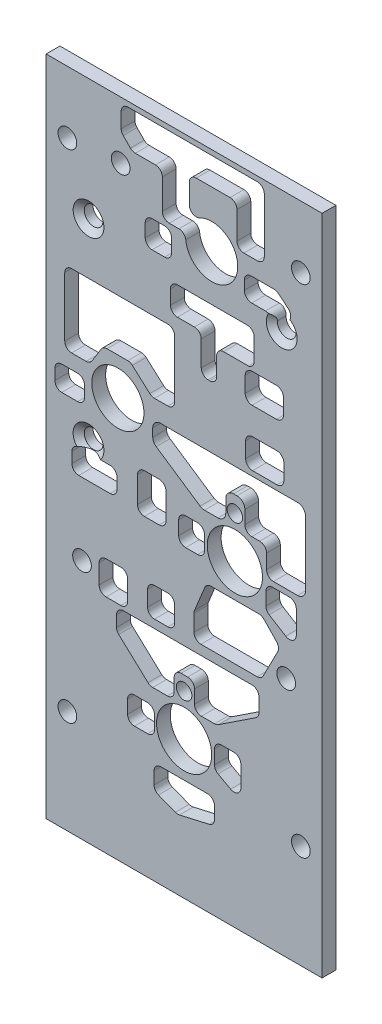
SolidWorks part; units mm, degrees
material "Acrylic (Medium-high impact)"
ref_plane "Front Plane" through (0, 0, 0) normal (0, 0, 1) x (1, 0, 0)
ref_plane "Top Plane" through (0, 0, 0) normal (0, 1, 0) x (1, 0, 0)
ref_plane "Right Plane" through (0, 0, 0) normal (1, 0, 0) x (0, 0, -1)
sketch "Sketch1" plane through (0, 0, 0) normal (0, 0, 1) x (1, 0, 0)
  line L8 (31.75, -152.4) -> (31.75, 0)
  line L9 (31.75, 0) -> (-31.75, 0)
  line L10 (-31.75, 0) -> (-31.75, -152.4)
  line L11 (-31.75, -152.4) -> (31.75, -152.4)
extrude "Boss-Extrude1" add sketch "Sketch1" against normal blind 3.175
hole_wizard "#6 Clearance Hole1" positions "Sketch3" profile "Sketch2" hole size "#6" standard "ANSI Inch" end condition up to next
sketch "Sketch3" plane through (0, 0, 0) normal (0, 0, 1) x (1, 0, 0)
  point P0 (-26.8605, -14.2875)
  point P2 (26.8605, -14.2875)
  point P4 (26.8605, -128.5875)
  point P6 (-26.8605, -128.5875)
sketch "Sketch2" plane through (-26.8605, -14.2875, 0) normal (1, 0, 0) x (0, -1, 0)
  line L0 (0, 0) -> (0, 3.175)
  line L1 (0, 3.175) -> (2.1526, 3.175)
  line L2 (2.1526, 3.175) -> (2.1526, 0)
  line L5 (2.1526, 0) -> (0, 0)
  line L11 (0, -6.35) -> (0, 107.95) construction
  dimension "Thru Hole Dia." = 4.3053
  dimension "Thru Hole Depth" = 3.175
hole_wizard "#6 Clearance Hole2" positions "Sketch5" profile "Sketch4" hole size "#6" standard "ANSI Inch" end condition up to next
sketch "Sketch5" plane through (0, 0, 0) normal (0, 0, 1) x (1, 0, 0)
  point P0 (-23.495, -96.8375)
  point P2 (23.495, -96.8375)
  point P4 (-14.605, -13.208)
sketch "Sketch4" plane through (-23.495, -96.8375, 0) normal (1, 0, 0) x (0, -1, 0)
  line L0 (0, 0) -> (0, 3.175)
  line L1 (0, 3.175) -> (2.1526, 3.175)
  line L2 (2.1526, 3.175) -> (2.1526, 0)
  line L5 (2.1526, 0) -> (0, 0)
  line L11 (0, -6.35) -> (0, 107.95) construction
  dimension "Thru Hole Dia." = 4.3053
  dimension "Thru Hole Depth" = 3.175
hole_wizard "1/2 (0.5) Diameter Hole1" positions "Sketch7" profile "Sketch6" hole size "1/2" standard "ANSI Inch" end condition up to next
sketch "Sketch7" plane through (0, 0, 0) normal (0, 0, 1) x (1, 0, 0)
  point P4 (11.684, -79.375)
  point P6 (0, -120.65)
sketch "Sketch6" plane through (11.684, -79.375, 0) normal (1, 0, 0) x (0, -1, 0)
  line L0 (0, 0) -> (0, 3.175)
  line L1 (0, 3.175) -> (6.35, 3.175)
  line L2 (6.35, 3.175) -> (6.35, 0)
  line L5 (6.35, 0) -> (0, 0)
  line L11 (0, -6.35) -> (0, 107.95) construction
  dimension "Thru Hole Dia." = 12.7
  dimension "Thru Hole Depth" = 3.175
hole_wizard "9/64 (0.14063) Diameter Hole1" positions "Sketch9" profile "Sketch8" hole size "9/64" standard "ANSI Inch" end condition up to next
sketch "Sketch9" plane through (0, 0, 0) normal (0, 0, 1) x (1, 0, 0)
  point P0 (0, -111.125)
  point P2 (11.684, -69.85)
sketch "Sketch8" plane through (0, -111.125, 0) normal (1, 0, 0) x (0, -1, 0)
  line L0 (0, 0) -> (0, 3.175)
  line L1 (0, 3.175) -> (1.786, 3.175)
  line L2 (1.786, 3.175) -> (1.786, 0)
  line L5 (1.786, 0) -> (0, 0)
  line L11 (0, -6.35) -> (0, 107.95) construction
  dimension "Thru Hole Dia." = 3.572
  dimension "Thru Hole Depth" = 3.175
hole_wizard "Ø12.0mm Dowel Hole1" positions "Sketch11" profile "Sketch10" hole size "Ø12.0" standard "ANSI Metric" end condition up to next
sketch "Sketch11" plane through (0, 0, 0) normal (0, 0, 1) x (1, 0, 0)
  point P0 (-15.24, -60.325)
  point P2 (6.35, -20.32)
sketch "Sketch10" plane through (-15.24, -60.325, 0) normal (1, 0, 0) x (0, -1, 0)
  line L0 (0, 0) -> (0, 3.175)
  line L1 (0, 3.175) -> (6, 3.175)
  line L2 (6, 3.175) -> (6, 0)
  line L5 (6, 0) -> (0, 0)
  line L11 (0, -6.35) -> (0, 107.95) construction
  dimension "Thru Hole Dia." = 12
  dimension "Thru Hole Depth" = 3.175
hole_wizard "CSK for #6 Flat Head Machine Screw (100)1" positions "Sketch12" profile "Sketch13" countersink size "#6" standard "ANSI Inch" end condition up to next
sketch "Sketch12" plane through (0, 0, 0) normal (0, 0, 1) x (1, 0, 0)
  circle A0 centre (-21.99, -72.39) radius 2.15 construction
  circle A1 centre (-21.99, -27.94) radius 2.15 construction
  circle A2 centre (22.46, -27.94) radius 2.15 construction
  point P0 (-21.99, -72.39)
  point P5 (-21.99, -27.94)
  point P7 (22.46, -27.94)
sketch "Sketch13" plane through (-21.99, -72.39, 0) normal (1, 0, 0) x (0, -1, 0)
  line L0 (0, 0) -> (0, 3.175)
  line L1 (0, 3.175) -> (2.1526, 3.175)
  line L2 (2.1526, 3.175) -> (2.1526, 1.1669)
  line L3 (2.1526, 1.1669) -> (3.5433, 0)
  line L5 (3.5433, 0) -> (0, 0)
  line L6 (-2.1526, 1.1669) -> (-3.5433, 0) construction
  line L11 (0, -6.35) -> (0, 107.95) construction
  dimension "Thru Hole Dia." = 4.3053
  dimension "Thru Hole Depth" = 3.175
  dimension "Near C'Sink Dia." = 7.0866
  dimension "Near C'Sink Angle" = 100
sketch "Sketch16" plane through (0, 0, 0) normal (0, 0, 1) x (1, 0, 0)
  line L0 (-8.9463, -22.2122) -> (-8.9463, -25.2501)
  line L1 (-12.8969, -1.1704) -> (16.8634, -1.1704)
  line L2 (18.4509, -2.7579) -> (18.4509, -15.3315)
  line L3 (16.8634, -16.919) -> (13.7539, -16.919)
  line L4 (12.1664, -15.3315) -> (12.1664, -9.0413)
  line L5 (10.5789, -7.4538) -> (2.798, -7.4538)
  line L6 (1.2105, -9.0413) -> (1.2105, -17.9777)
  line L7 (-0.377, -19.5652) -> (-3.4256, -19.5652)
  line L8 (-5.0131, -17.9777) -> (-5.0131, -11.1146)
  line L9 (-6.6006, -9.5271) -> (-11.2247, -9.5271)
  line L10 (-12.3472, -9.0621) -> (-14.0195, -7.3899)
  line L11 (-14.4844, -6.2674) -> (-14.4844, -2.7579)
  line L12 (-7.3588, -20.6247) -> (-4.4726, -20.6247)
  line L13 (-2.8851, -22.2122) -> (-2.8851, -25.2501)
  line L14 (-4.4726, -26.8376) -> (-7.3588, -26.8376)
  line L19 (-1.5492, -30.8932) -> (14.5429, -30.8932)
  line L20 (16.1304, -32.4807) -> (16.1304, -37.3513)
  line L24 (-25.8787, -39.8413) -> (-3.7395, -39.8413)
  line L25 (-2.152, -41.4288) -> (-2.152, -54.5712)
  line L26 (-3.7395, -56.1587) -> (-6.8312, -56.1587)
  line L27 (-7.8927, -55.7517) -> (-11.9102, -52.1393)
  line L28 (-12.9716, -51.7323) -> (-17.7428, -51.7323)
  line L29 (-19.0941, -52.4865) -> (-21.1969, -55.8964)
  line L30 (-22.5481, -56.6506) -> (-25.8787, -56.6506)
  line L31 (-27.4662, -55.0631) -> (-27.4662, -41.4288)
  line L32 (-28.1475, -60.0018) -> (-24.5023, -60.0018)
  line L33 (-22.9148, -61.5893) -> (-22.9148, -64.0639)
  line L34 (-24.5023, -65.6514) -> (-28.1475, -65.6514)
  line L35 (-29.735, -64.0639) -> (-29.735, -61.5893)
  line L36 (-5.4046, -60.4477) -> (26.1238, -60.4477)
  line L37 (27.9362, -62.2601) -> (27.9362, -77.1663)
  line L38 (26.1238, -78.9787) -> (20.5606, -78.9787)
  line L40 (13.9861, -70.9353) -> (13.9861, -67.9021)
  line L41 (12.1737, -66.0897) -> (11.3976, -66.0897)
  line L42 (9.5852, -67.9021) -> (9.5852, -70.8813)
  line L43 (7.7728, -72.6937) -> (4.6983, -72.6937)
  line L44 (3.687, -72.3854) -> (-6.4159, -65.5923)
  line L45 (-7.217, -64.0882) -> (-7.217, -62.2601)
  line L46 (-10.7238, -73.3212) -> (-10.7238, -79.2675)
  line L47 (-9.1363, -80.855) -> (-5.7548, -80.855)
  line L48 (-4.1673, -79.2675) -> (-4.1673, -73.3212)
  line L49 (-5.7548, -71.7337) -> (-9.1363, -71.7337)
  line L50 (-24.2328, -74.6188) -> (-17.0395, -74.6188)
  line L51 (-15.452, -76.2063) -> (-15.452, -78.6488)
  line L52 (-17.0395, -80.2363) -> (-24.2328, -80.2363)
  line L53 (-25.8203, -78.6488) -> (-25.8203, -76.2063)
  line L54 (0.3424, -75.984) -> (3.1108, -75.984)
  line L55 (4.6983, -77.5715) -> (4.6983, -80.74)
  line L56 (3.1108, -82.3275) -> (0.3424, -82.3275)
  line L57 (-1.2451, -80.74) -> (-1.2451, -77.5715)
  line L58 (24.2295, -80.2363) -> (20.397, -80.2363)
  line L59 (18.8095, -81.8238) -> (18.8095, -84.7457)
  line L60 (19.5645, -86.0974) -> (23.397, -88.4579)
  line L61 (25.817, -87.1062) -> (25.817, -81.8238)
  line L62 (6.2151, -87.1062) -> (17.232, -87.1062)
  line L66 (16.7933, -99.8291) -> (3.862, -99.8291)
  line L67 (2.2745, -98.2416) -> (2.2745, -94.4383)
  line L68 (2.3929, -93.8366) -> (4.7461, -88.092)
  line L70 (18.2045, -98.9687) -> (21.5565, -92.4623)
  line L71 (21.2917, -90.6372) -> (18.3784, -87.5956)
  line L72 (-17.9633, -93.6958) -> (-14.5591, -93.6958)
  line L73 (-12.9716, -95.2833) -> (-12.9716, -99.7266)
  line L74 (-14.5591, -101.3141) -> (-17.9633, -101.3141)
  line L75 (-19.5508, -99.7266) -> (-19.5508, -95.2833)
  line L76 (-6.8147, -93.4357) -> (-3.7395, -93.4357)
  line L77 (-2.152, -95.0232) -> (-2.152, -98.5745)
  line L78 (-3.7395, -100.162) -> (-6.8147, -100.162)
  line L79 (-8.4022, -98.5745) -> (-8.4022, -95.0232)
  line L80 (-13.9592, -102.0646) -> (15.6445, -102.0646)
  line L81 (17.232, -103.6521) -> (17.232, -106.8148)
  line L82 (16.5194, -108.1395) -> (7.8736, -113.8498)
  line L83 (6.9987, -114.1127) -> (3.9804, -114.1127)
  line L84 (2.3929, -112.5252) -> (2.3929, -109.4802)
  line L85 (0.8054, -107.8927) -> (-0.6914, -107.8927)
  line L86 (-2.2789, -109.4802) -> (-2.2789, -112.4007)
  line L87 (-3.8664, -113.9882) -> (-7.2276, -113.9882)
  line L88 (-8.3063, -113.5654) -> (-15.0379, -107.3311)
  line L89 (-15.5467, -106.1663) -> (-15.5467, -103.6521)
  line L90 (-11.4225, -117.5966) -> (-8.4022, -117.5966)
  line L91 (-6.8147, -119.1841) -> (-6.8147, -122.2054)
  line L92 (-8.4022, -123.7929) -> (-11.4225, -123.7929)
  line L93 (-13.01, -122.2054) -> (-13.01, -119.1841)
  line L94 (13.0588, -123.895) -> (13.0588, -119.1357)
  line L95 (11.4713, -117.5482) -> (8.5862, -117.5482)
  line L96 (6.9987, -119.1357) -> (6.9987, -122.3052)
  line L97 (7.82, -123.6955) -> (10.7052, -125.2854)
  line L98 (-5.3306, -128.8529) -> (5.3948, -128.8529)
  line L99 (6.9823, -130.4404) -> (6.9823, -133.2123)
  line L100 (5.7484, -134.7599) -> (-1.0759, -136.3192)
  line L101 (-2.002, -136.2523) -> (-5.9031, -134.7439)
  line L102 (-6.9181, -133.2633) -> (-6.9181, -130.4404)
  line L103 (18.9731, -77.3912) -> (18.9731, -74.1103)
  line L104 (17.3856, -72.5228) -> (15.5736, -72.5228)
  line L111 (15.6446, -46.3047) -> (21.2651, -46.3047)
  line L112 (14.0571, -44.7172) -> (14.0571, -41.1264)
  line L113 (15.6446, -39.5389) -> (21.2651, -39.5389)
  line L114 (22.8526, -41.1264) -> (22.8526, -44.7172)
  line L116 (3.9429, -38.9388) -> (3.9429, -44.7172)
  line L117 (5.5304, -46.3047) -> (5.9063, -46.3047)
  line L118 (7.4938, -44.7172) -> (7.4938, -40.4965)
  line L119 (9.0813, -38.909) -> (14.8494, -38.909)
  line L120 (2.3554, -37.3513) -> (-1.5492, -37.3513)
  line L121 (-3.1367, -35.7638) -> (-3.1367, -32.4807)
  line L122 (15.7456, -59.2937) -> (21.3661, -59.2937)
  line L123 (14.1581, -57.7062) -> (14.1581, -54.1154)
  line L124 (15.7456, -52.5279) -> (21.3661, -52.5279)
  line L125 (22.9536, -54.1154) -> (22.9536, -57.7062)
  line L132 (13.8618, -22.2377) -> (13.8618, -24.2911)
  line L133 (15.5562, -25.9855) -> (22.1227, -25.9855)
  line L134 (15.4493, -20.6502) -> (20.6723, -20.6502)
  line L135 (21.6766, -21.0082) -> (23.9579, -22.8717)
  line L136 (23.4877, -25.5961) -> (22.6568, -25.893)
  arc A0 (16.8634, -1.1704) -> (18.4509, -2.7579) centre (16.8634, -2.7579) cw
  arc A1 (18.4509, -15.3315) -> (16.8634, -16.919) centre (16.8634, -15.3315) cw
  arc A2 (13.7539, -16.919) -> (12.1664, -15.3315) centre (13.7539, -15.3315) cw
  arc A3 (12.1664, -9.0413) -> (10.5789, -7.4538) centre (10.5789, -9.0413) ccw
  arc A4 (2.798, -7.4538) -> (1.2105, -9.0413) centre (2.798, -9.0413) ccw
  arc A5 (1.2105, -17.9777) -> (-0.377, -19.5652) centre (-0.377, -17.9777) cw
  arc A6 (-3.4256, -19.5652) -> (-5.0131, -17.9777) centre (-3.4256, -17.9777) cw
  arc A7 (-5.0131, -11.1146) -> (-6.6006, -9.5271) centre (-6.6006, -11.1146) ccw
  arc A8 (-11.2247, -9.5271) -> (-12.3472, -9.0621) centre (-11.2247, -7.9396) cw
  arc A9 (-14.0195, -7.3899) -> (-14.4844, -6.2674) centre (-12.8969, -6.2674) cw
  arc A10 (-12.8969, -1.1704) -> (-14.4844, -2.7579) centre (-12.8969, -2.7579) ccw
  arc A11 (-7.3588, -26.8376) -> (-8.9463, -25.2501) centre (-7.3588, -25.2501) cw
  arc A12 (-2.8851, -25.2501) -> (-4.4726, -26.8376) centre (-4.4726, -25.2501) cw
  arc A13 (-4.4726, -20.6247) -> (-2.8851, -22.2122) centre (-4.4726, -22.2122) cw
  arc A14 (-7.3588, -20.6247) -> (-8.9463, -22.2122) centre (-7.3588, -22.2122) ccw
  arc A19 (14.5429, -30.8932) -> (16.1304, -32.4807) centre (14.5429, -32.4807) cw
  arc A20 (16.1304, -37.3513) -> (14.8494, -38.909) centre (14.5429, -37.3513) cw
  arc A23 (-1.5492, -30.8932) -> (-3.1367, -32.4807) centre (-1.5492, -32.4807) ccw
  arc A24 (-25.8787, -56.6506) -> (-27.4662, -55.0631) centre (-25.8787, -55.0631) cw
  arc A25 (-21.1969, -55.8964) -> (-22.5481, -56.6506) centre (-22.5481, -55.0631) cw
  arc A26 (-17.7428, -51.7323) -> (-19.0941, -52.4865) centre (-17.7428, -53.3198) ccw
  arc A27 (-11.9102, -52.1393) -> (-12.9716, -51.7323) centre (-12.9716, -53.3198) ccw
  arc A28 (-6.8312, -56.1587) -> (-7.8927, -55.7517) centre (-6.8312, -54.5712) cw
  arc A29 (-2.152, -54.5712) -> (-3.7395, -56.1587) centre (-3.7395, -54.5712) cw
  arc A30 (-3.7395, -39.8413) -> (-2.152, -41.4288) centre (-3.7395, -41.4288) cw
  arc A31 (-25.8787, -39.8413) -> (-27.4662, -41.4288) centre (-25.8787, -41.4288) ccw
  arc A32 (-28.1475, -65.6514) -> (-29.735, -64.0639) centre (-28.1475, -64.0639) cw
  arc A33 (-22.9148, -64.0639) -> (-24.5023, -65.6514) centre (-24.5023, -64.0639) cw
  arc A34 (-24.5023, -60.0018) -> (-22.9148, -61.5893) centre (-24.5023, -61.5893) cw
  arc A35 (-28.1475, -60.0018) -> (-29.735, -61.5893) centre (-28.1475, -61.5893) ccw
  arc A36 (26.1238, -60.4477) -> (27.9362, -62.2601) centre (26.1238, -62.2601) cw
  arc A37 (27.9362, -77.1663) -> (26.1238, -78.9787) centre (26.1238, -77.1663) cw
  arc A40 (13.9861, -67.9021) -> (12.1737, -66.0897) centre (12.1737, -67.9021) ccw
  arc A41 (11.3976, -66.0897) -> (9.5852, -67.9021) centre (11.3976, -67.9021) ccw
  arc A42 (9.5852, -70.8813) -> (7.7728, -72.6937) centre (7.7728, -70.8813) cw
  arc A43 (4.6983, -72.6937) -> (3.687, -72.3854) centre (4.6983, -70.8813) cw
  arc A44 (-6.4159, -65.5923) -> (-7.217, -64.0882) centre (-5.4046, -64.0882) cw
  arc A45 (-5.4046, -60.4477) -> (-7.217, -62.2601) centre (-5.4046, -62.2601) ccw
  arc A46 (-4.1673, -73.3212) -> (-5.7548, -71.7337) centre (-5.7548, -73.3212) ccw
  arc A47 (-5.7548, -80.855) -> (-4.1673, -79.2675) centre (-5.7548, -79.2675) ccw
  arc A48 (-10.7238, -79.2675) -> (-9.1363, -80.855) centre (-9.1363, -79.2675) ccw
  arc A49 (-10.7238, -73.3212) -> (-9.1363, -71.7337) centre (-9.1363, -73.3212) cw
  arc A50 (-24.2328, -80.2363) -> (-25.8203, -78.6488) centre (-24.2328, -78.6488) cw
  arc A51 (-15.452, -78.6488) -> (-17.0395, -80.2363) centre (-17.0395, -78.6488) cw
  arc A52 (-17.0395, -74.6188) -> (-15.452, -76.2063) centre (-17.0395, -76.2063) cw
  arc A53 (-24.2328, -74.6188) -> (-25.8203, -76.2063) centre (-24.2328, -76.2063) ccw
  arc A54 (3.1108, -75.984) -> (4.6983, -77.5715) centre (3.1108, -77.5715) cw
  arc A55 (4.6983, -80.74) -> (3.1108, -82.3275) centre (3.1108, -80.74) cw
  arc A56 (0.3424, -82.3275) -> (-1.2451, -80.74) centre (0.3424, -80.74) cw
  arc A57 (0.3424, -75.984) -> (-1.2451, -77.5715) centre (0.3424, -77.5715) ccw
  arc A58 (23.397, -88.4579) -> (25.817, -87.1062) centre (24.2295, -87.1062) ccw
  arc A59 (18.8095, -84.7457) -> (19.5645, -86.0974) centre (20.397, -84.7457) ccw
  arc A60 (20.397, -80.2363) -> (18.8095, -81.8238) centre (20.397, -81.8238) ccw
  arc A61 (24.2295, -80.2363) -> (25.817, -81.8238) centre (24.2295, -81.8238) cw
  arc A65 (3.862, -99.8291) -> (2.2745, -98.2416) centre (3.862, -98.2416) cw
  arc A66 (2.2745, -94.4383) -> (2.3929, -93.8366) centre (3.862, -94.4383) cw
  arc A67 (6.2151, -87.1062) -> (4.7461, -88.092) centre (6.2151, -88.6937) ccw
  arc A68 (16.7933, -99.8291) -> (18.2045, -98.9687) centre (16.7933, -98.2416) ccw
  arc A69 (21.5565, -92.4623) -> (21.2917, -90.6372) centre (20.1453, -91.7353) ccw
  arc A70 (17.232, -87.1062) -> (18.3784, -87.5956) centre (17.232, -88.6937) cw
  arc A71 (-17.9633, -101.3141) -> (-19.5508, -99.7266) centre (-17.9633, -99.7266) cw
  arc A72 (-12.9716, -99.7266) -> (-14.5591, -101.3141) centre (-14.5591, -99.7266) cw
  arc A73 (-14.5591, -93.6958) -> (-12.9716, -95.2833) centre (-14.5591, -95.2833) cw
  arc A74 (-17.9633, -93.6958) -> (-19.5508, -95.2833) centre (-17.9633, -95.2833) ccw
  arc A75 (-6.8147, -100.162) -> (-8.4022, -98.5745) centre (-6.8147, -98.5745) cw
  arc A76 (-2.152, -98.5745) -> (-3.7395, -100.162) centre (-3.7395, -98.5745) cw
  arc A77 (-3.7395, -93.4357) -> (-2.152, -95.0232) centre (-3.7395, -95.0232) cw
  arc A78 (-6.8147, -93.4357) -> (-8.4022, -95.0232) centre (-6.8147, -95.0232) ccw
  arc A79 (-7.2276, -113.9882) -> (-8.3063, -113.5654) centre (-7.2276, -112.4007) cw
  arc A80 (-15.0379, -107.3311) -> (-15.5467, -106.1663) centre (-13.9592, -106.1663) cw
  arc A81 (-13.9592, -102.0646) -> (-15.5467, -103.6521) centre (-13.9592, -103.6521) ccw
  arc A82 (15.6445, -102.0646) -> (17.232, -103.6521) centre (15.6445, -103.6521) cw
  arc A83 (17.232, -106.8148) -> (16.5194, -108.1395) centre (15.6445, -106.8148) cw
  arc A84 (7.8736, -113.8498) -> (6.9987, -114.1127) centre (6.9987, -112.5252) cw
  arc A85 (3.9804, -114.1127) -> (2.3929, -112.5252) centre (3.9804, -112.5252) cw
  arc A86 (-2.2789, -112.4007) -> (-3.8664, -113.9882) centre (-3.8664, -112.4007) cw
  arc A87 (2.3929, -109.4802) -> (0.8054, -107.8927) centre (0.8054, -109.4802) ccw
  arc A88 (-0.6914, -107.8927) -> (-2.2789, -109.4802) centre (-0.6914, -109.4802) ccw
  arc A89 (-8.4022, -117.5966) -> (-6.8147, -119.1841) centre (-8.4022, -119.1841) cw
  arc A90 (-6.8147, -122.2054) -> (-8.4022, -123.7929) centre (-8.4022, -122.2054) cw
  arc A91 (-11.4225, -123.7929) -> (-13.01, -122.2054) centre (-11.4225, -122.2054) cw
  arc A92 (-11.4225, -117.5966) -> (-13.01, -119.1841) centre (-11.4225, -119.1841) ccw
  arc A93 (6.9987, -122.3052) -> (7.82, -123.6955) centre (8.5862, -122.3052) ccw
  arc A94 (8.5862, -117.5482) -> (6.9987, -119.1357) centre (8.5862, -119.1357) ccw
  arc A95 (13.0588, -119.1357) -> (11.4713, -117.5482) centre (11.4713, -119.1357) ccw
  arc A96 (13.0588, -123.895) -> (10.7052, -125.2854) centre (11.4713, -123.895) cw
  arc A97 (5.3948, -128.8529) -> (6.9823, -130.4404) centre (5.3948, -130.4404) cw
  arc A98 (6.9823, -133.2123) -> (5.7484, -134.7599) centre (5.3948, -133.2123) cw
  arc A99 (-1.0759, -136.3192) -> (-2.002, -136.2523) centre (-1.4295, -134.7716) cw
  arc A100 (-5.9031, -134.7439) -> (-6.9181, -133.2633) centre (-5.3306, -133.2633) cw
  arc A101 (-5.3306, -128.8529) -> (-6.9181, -130.4404) centre (-5.3306, -130.4404) ccw
  arc A102 (20.5606, -78.9787) -> (18.9731, -77.3912) centre (20.5606, -77.3912) cw
  arc A103 (13.9861, -70.9353) -> (15.5736, -72.5228) centre (15.5736, -70.9353) ccw
  arc A104 (18.9731, -74.1103) -> (17.3856, -72.5228) centre (17.3856, -74.1103) ccw
  arc A105 (22.8526, -44.7172) -> (21.2651, -46.3047) centre (21.2651, -44.7172) cw
  arc A106 (14.0571, -44.7172) -> (15.6446, -46.3047) centre (15.6446, -44.7172) ccw
  arc A107 (14.0571, -41.1264) -> (15.6446, -39.5389) centre (15.6446, -41.1264) cw
  arc A108 (21.2651, -39.5389) -> (22.8526, -41.1264) centre (21.2651, -41.1264) cw
  arc A109 (7.4938, -40.4965) -> (9.0813, -38.909) centre (9.0813, -40.4965) cw
  arc A110 (2.3554, -37.3513) -> (3.9429, -38.9388) centre (2.3554, -38.9388) cw
  arc A111 (-1.5492, -37.3513) -> (-3.1367, -35.7638) centre (-1.5492, -35.7638) cw
  arc A112 (3.9429, -44.7172) -> (5.5304, -46.3047) centre (5.5304, -44.7172) ccw
  arc A113 (5.9063, -46.3047) -> (7.4938, -44.7172) centre (5.9063, -44.7172) ccw
  arc A114 (22.9536, -57.7062) -> (21.3661, -59.2937) centre (21.3661, -57.7062) cw
  arc A115 (14.1581, -57.7062) -> (15.7456, -59.2937) centre (15.7456, -57.7062) ccw
  arc A116 (14.1581, -54.1154) -> (15.7456, -52.5279) centre (15.7456, -54.1154) cw
  arc A117 (21.3661, -52.5279) -> (22.9536, -54.1154) centre (21.3661, -54.1154) cw
  arc A121 (15.4493, -20.6502) -> (13.8618, -22.2377) centre (15.4493, -22.2377) ccw
  arc A123 (13.8618, -24.2911) -> (15.5562, -25.9855) centre (15.5562, -24.2911) ccw
  arc A127 (20.6723, -20.6502) -> (21.6766, -21.0082) centre (20.6723, -22.2377) cw
  arc A128 (22.1227, -25.9855) -> (22.6568, -25.893) centre (22.1227, -24.398) ccw
  arc A129 (23.9579, -22.8717) -> (23.4877, -25.5961) centre (22.9536, -24.1011) cw
  dimension "D1" = 1.5875
  dimension "D2" = 1.5875
  dimension "D3" = 1.5875
  dimension "D4" = 1.5875
  dimension "D5" = 1.5875
  dimension "D6" = 1.5875
  dimension "D7" = 1.8124
  dimension "D8" = 1.5875
  dimension "D9" = 1.5875
  dimension "D10" = 1.5875
  dimension "D11" = 1.5875
  dimension "D12" = 1.5875
  dimension "D13" = 1.5875
  dimension "D14" = 1.5875
  dimension "D15" = 1.5875
  dimension "D16" = 1.5875
  dimension "D17" = 1.5875
  dimension "D18" = 1.5875
  dimension "D19" = 1.5875
  dimension "D20" = 1.5875
  dimension "D21" = 1.5875
  dimension "D22" = 1.5875
  dimension "D23" = 1.5875
  dimension "D24" = 1.5875
  dimension "D25" = 1.5875
extrude "Cut-Extrude1" cut sketch "Sketch16" against normal through all
fillet "Fillet1" radius 1.5875 4 edges at (21.5579, -25.9855, -2.1709) (22.8518, -25.8233, -2.1709) (0.4298, -19.3449, -1.5875) (1.2105, -17.224, -1.5875)
